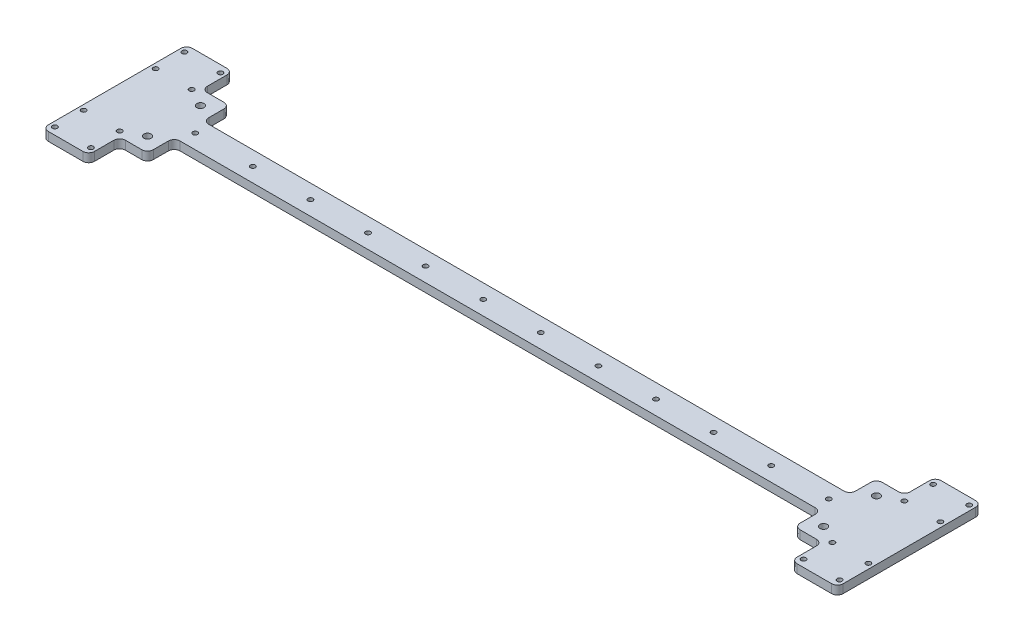
SolidWorks part; units mm, degrees
ref_plane "Front Plane" through (0, 0, 0) normal (0, 0, 1) x (1, 0, 0)
ref_plane "Top Plane" through (0, 0, 0) normal (0, 1, 0) x (1, 0, 0)
ref_plane "Right Plane" through (0, 0, 0) normal (1, 0, 0) x (0, 0, -1)
sketch "Sketch1" plane through (0, 0, 0) normal (0, 1, 0) x (1, 0, 0)
  line L1 (0, 0) -> (552, 0)
  line L2 (0, 0) -> (0, 20)
  line L3 (0, 20) -> (552, 20)
  line L4 (552, 0) -> (552, 20)
  dimension "D1" = 20
  dimension "D2" = 552
extrude "Boss-Extrude1" add sketch "Sketch1" along normal blind 6
ref_plane "Plane1" through (276, 0, 0) normal (1, 0, 0) x (0, 0, -1)
sketch "Sketch3" plane through (0, 0, 0) normal (0, -1, 0) x (1, 0, 0)
  line L0 (0, 0) -> (552, 0) construction
  line L1 (0, -60) -> (32, -60)
  line L2 (0, -60) -> (0, 40)
  line L3 (0, 40) -> (32, 40)
  line L4 (32, -60) -> (32, 40)
  dimension "D1" = 32
  dimension "D2" = 100
  dimension "D3" = 40
extrude "Boss-Extrude2" add sketch "Sketch3" against normal up to surface (6 mm away) up to face at (276, 6, -10)
sketch "Sketch4" plane through (0, 6, 0) normal (0, 1, 0) x (1, 0, 0)
  line L0 (16, -40) -> (16, 60)
  line L1 (0, -40) -> (32, -40) construction
  line L2 (32, 60) -> (0, 60) construction
  line L4 (3.5, -35) -> (28.5, -35)
  line L5 (3.5, -35) -> (3.5, -15)
  line L6 (3.5, -15) -> (28.5, -15)
  line L7 (28.5, -35) -> (28.5, -15)
  line L8 (3.5, -35) -> (28.5, -15) construction
  line L9 (3.5, -15) -> (28.5, -35) construction
  line L10 (3.5, 35) -> (28.5, 35)
  line L11 (3.5, 35) -> (3.5, 55)
  line L12 (3.5, 55) -> (28.5, 55)
  line L13 (28.5, 35) -> (28.5, 55)
  line L14 (3.5, 35) -> (28.5, 55) construction
  line L15 (3.5, 55) -> (28.5, 35) construction
  point P6 (16, -25)
  point P11 (16, 45)
  point P16 (0, 0)
  dimension "D1" = 20
  dimension "D2" = 25
  dimension "D3" = 5
  dimension "D4" = 5
sketch "Sketch7" plane through (0, 6, 0) normal (0, 1, 0) x (1, 0, 0)
  line L0 (276, 0) -> (276, 20) construction
  line L1 (32, 0) -> (552, 0) construction
  line L2 (552, 20) -> (32, 20) construction
  line L3 (276, -3.3) -> (276, 3.3) construction
  line L4 (276, 10) -> (256, 10) construction
  point P11 (256, 10)
  point P13 (216, 10)
  point P14 (176, 10)
  point P15 (136, 10)
  point P16 (96, 10)
  point P17 (56, 10)
  dimension "D1" = 20
  dimension "D3" = 40
  dimension "D2" = 6
hole_wizard "M3 Clearance Hole1" positions "Sketch5" profile "Sketch6" hole size "M3" standard "ANSI Metric" end condition through all
sketch "Sketch5" plane through (0, 6, 0) normal (0, 1, 0) x (1, 0, 0)
  point P0 (3.5, -35)
  point P3 (3.5, -15)
  point P6 (28.5, -15)
  point P9 (28.5, -35)
  point P12 (3.5, 55)
  point P15 (28.5, 55)
  point P18 (28.5, 35)
  point P21 (3.5, 35)
  point P25 (56, 10)
  point P28 (96, 10)
  point P31 (136, 10)
  point P34 (176, 10)
  point P37 (216, 10)
  point P40 (256, 10)
sketch "Sketch6" plane through (3.5, 6, 35) normal (1, 0, 0) x (0, 0, 1)
  line L0 (0, 0) -> (0, 6)
  line L1 (0, 6) -> (1.7, 6)
  line L2 (1.7, 6) -> (1.7, 0)
  line L5 (1.7, 0) -> (0, 0)
  line L11 (0, -6.35) -> (0, 107.95) construction
  dimension "Thru Hole Dia." = 3.4
  dimension "Thru Hole Depth" = 6
sketch "Sketch8" plane through (0, 6, 0) normal (0, 1, 0) x (1, 0, 0)
  line L0 (56.3721, 22) -> (87.6482, 22) construction
  line L1 (552, 20) -> (32, 20) construction
  line L2 (105.1095, -2) -> (88.5975, -2) construction
  line L3 (32, 0) -> (552, 0) construction
  line L4 (34.8662, 60) -> (34.8662, 28.3662) construction
  line L5 (34.8662, -40) -> (34.8662, -8.3662) construction
  line L6 (28.5, -40) -> (28.5, 60) construction
  line L7 (0, -40) -> (32, -40) construction
  line L8 (32, 60) -> (0, 60) construction
  line L9 (28.5, 35) -> (28.5, 55) construction
  circle A0 centre (41.2324, 28.3662) radius 6.3662
  circle A1 centre (28.5, 60) radius 6.3662
  circle A2 centre (28.5, -40) radius 6.3662
  circle A3 centre (41.2324, -8.3662) radius 6.3662
  circle A4 centre (41.2324, 28.3662) radius 10.16
  circle A5 centre (41.2324, -8.3662) radius 10.16
  circle A6 centre (28.5, -40) radius 10.16
  circle A7 centre (28.5, 60) radius 10.16
  point P24 (0, 0)
  point P27 (34.8662, -8.3662)
  dimension "D3" = 12.7324
  dimension "D4" = 20.32
  dimension "D1" = 2
  dimension "D2" = 2
sketch "Sketch10" plane through (0, 6, 0) normal (0, 1, 0) x (1, 0, 0)
  line L1 (32, 0) -> (51.3924, 0)
  line L2 (32, 0) -> (32, -18.5262)
  line L3 (32, -18.5262) -> (51.3924, -18.5262)
  line L4 (51.3924, 0) -> (51.3924, -18.5262)
  line L5 (32, 20) -> (51.3924, 20)
  line L6 (32, 20) -> (32, 38.5262)
  line L7 (32, 38.5262) -> (51.3924, 38.5262)
  line L8 (51.3924, 20) -> (51.3924, 38.5262)
  circle A0 centre (41.2324, -8.3662) radius 10.16 construction
  circle A1 centre (41.2324, -8.3662) radius 2.525
  circle A2 centre (41.2324, 28.3662) radius 2.525
  dimension "D1" = 5.05
extrude "Boss-Extrude3" add sketch "Sketch10" against normal up to surface (6 mm away) up to face at (3.5, 0, 36.7)
fillet "Fillet2" radius 4 10 edges at (32, 3, 40) (0, 3, 40) (0, 3, -60) (32, 3, -60) (32, 3, -38.5262) (51.3924, 3, -38.5262) (51.3924, 3, -20) (51.3924, 3, 18.5262) (51.3924, 3, 0) (32, 3, 18.5262)
mirror "Mirror1" about plane through (276, 0, 0) normal (1, 0, 0) of "Fillet2", "Boss-Extrude3", "M3 Clearance Hole1", "Boss-Extrude2"
